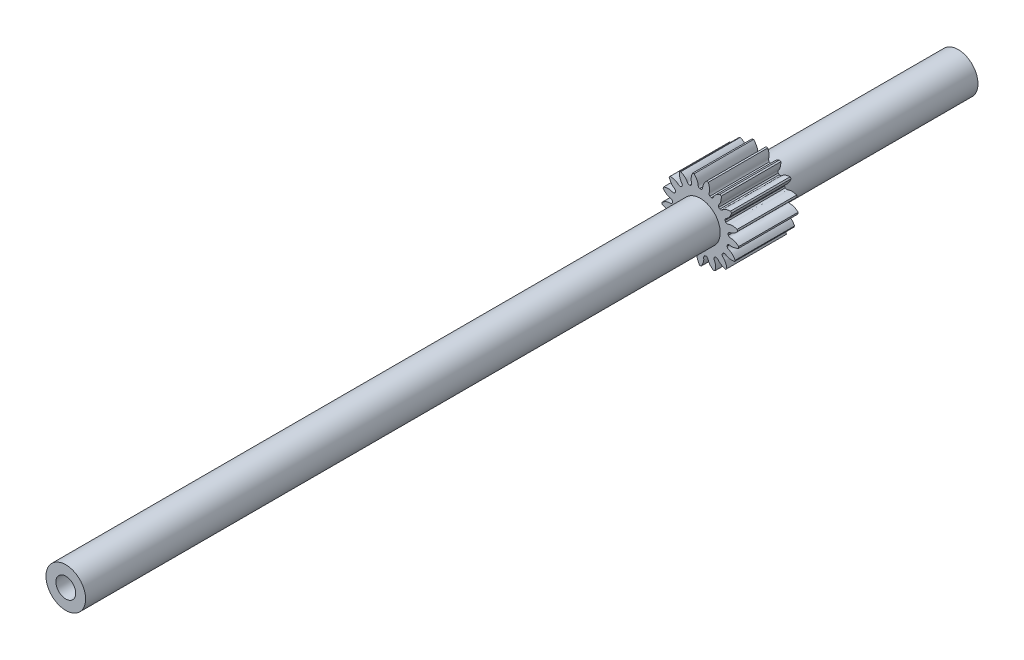
SolidWorks part; units mm, degrees
ref_plane "前视基准面" through (0, 0, 0) normal (0, 0, 1) x (1, 0, 0)
ref_plane "上视基准面" through (0, 0, 0) normal (0, 1, 0) x (1, 0, 0)
ref_plane "右视基准面" through (0, 0, 0) normal (1, 0, 0) x (0, 0, -1)
sketch "草图1" plane through (0, 0, 0) normal (0, 0, 1) x (1, 0, 0)
  circle A0 centre (0, 0) radius 19.4
extrude "凸台-拉伸1" add sketch "草图1" along normal blind 30
ref_axis "基准轴1" through (0, 0, -1.5) along (0, 0, 1)
sketch "草图2" plane through (0, 0, 0) normal (0, 0, 1) x (1, 0, 0)
  line L0 (0, 0) -> (0, 19.4) construction
  circle A0 centre (0, 0) radius 19.4 construction
  arc A1 (0.3734, 14.0951) -> (-0.3734, 14.0951) centre (0, 0) ccw
  arc A2 (7.0885, 21.9309) -> (-7.0885, 21.9309) centre (0, 0) ccw
  spline S0 degree 3 poles (0.3734, 14.0951) (1.3131, 14.5845) (1.1044, 15.3893) (1.2766, 16.1296) (1.29, 16.1823) (1.306, 16.2408) (1.3251, 16.3052) (1.3474, 16.3752) (1.3731, 16.4508) (1.4025, 16.5319) (1.4359, 16.6184) (1.4733, 16.7101) (1.5152, 16.8068) (1.5616, 16.9086) (1.6128, 17.0151) (1.669, 17.1264) (1.7304, 17.2421) (1.7972, 17.3621) (1.8696, 17.4863) (1.9478, 17.6145) (2.032, 17.7465) (2.1224, 17.8821) (2.2191, 18.0211) (2.3223, 18.1634) (2.4322, 18.3086) (2.5489, 18.4566) (2.6727, 18.6072) (2.8035, 18.7601) (2.9417, 18.9152) (3.0873, 19.0722) (3.2404, 19.2308) (3.4012, 19.3908) (3.5698, 19.552) (3.7462, 19.7141) (3.9307, 19.8769) (4.1233, 20.0401) (4.324, 20.2035) (4.533, 20.3667) (4.7503, 20.5295) (4.9761, 20.6917) (5.2103, 20.853) (5.453, 21.0131) (5.7043, 21.1717) (5.9641, 21.3286) (6.2326, 21.4834) (6.6059, 21.6888) (6.8932, 21.8358) (7.0885, 21.9309) knots 0 0 0 0 0.204302 0.208797 0.213892 0.219586 0.22588 0.232773 0.240266 0.248357 0.257049 0.266339 0.276229 0.286719 0.297808 0.309496 0.321783 0.33467 0.348157 0.362243 0.376928 0.392212 0.408096 0.42458 0.441663 0.459345 0.477626 0.496507 0.515988 0.536068 0.556747 0.578025 0.599903 0.622381 0.645457 0.669133 0.693409 0.718284 0.743758 0.769832 0.796505 0.823778 0.851649 0.880121 0.909192 0.938862 1 1 1 1
  spline S1 degree 3 poles (-0.3734, 14.0951) (-1.3131, 14.5845) (-1.1044, 15.3893) (-1.2766, 16.1296) (-1.29, 16.1823) (-1.306, 16.2408) (-1.3251, 16.3052) (-1.3474, 16.3752) (-1.3731, 16.4508) (-1.4025, 16.5319) (-1.4359, 16.6184) (-1.4733, 16.7101) (-1.5152, 16.8068) (-1.5616, 16.9086) (-1.6128, 17.0151) (-1.669, 17.1264) (-1.7304, 17.2421) (-1.7972, 17.3621) (-1.8696, 17.4863) (-1.9478, 17.6145) (-2.032, 17.7465) (-2.1224, 17.8821) (-2.2191, 18.0211) (-2.3223, 18.1634) (-2.4322, 18.3086) (-2.5489, 18.4566) (-2.6727, 18.6072) (-2.8035, 18.7601) (-2.9417, 18.9152) (-3.0873, 19.0722) (-3.2404, 19.2308) (-3.4012, 19.3908) (-3.5698, 19.552) (-3.7462, 19.7141) (-3.9307, 19.8769) (-4.1233, 20.0401) (-4.324, 20.2035) (-4.533, 20.3667) (-4.7503, 20.5295) (-4.9761, 20.6917) (-5.2103, 20.853) (-5.453, 21.0131) (-5.7043, 21.1717) (-5.9641, 21.3286) (-6.2326, 21.4834) (-6.6059, 21.6888) (-6.8932, 21.8358) (-7.0885, 21.9309) knots 0 0 0 0 0.204302 0.208797 0.213892 0.219586 0.22588 0.232773 0.240266 0.248357 0.257049 0.266339 0.276229 0.286719 0.297808 0.309496 0.321783 0.33467 0.348157 0.362243 0.376928 0.392212 0.408096 0.42458 0.441663 0.459345 0.477626 0.496507 0.515988 0.536068 0.556747 0.578025 0.599903 0.622381 0.645457 0.669133 0.693409 0.718284 0.743758 0.769832 0.796505 0.823778 0.851649 0.880121 0.909192 0.938862 1 1 1 1
extrude "切除-拉伸1" cut sketch "草图2" along normal through all
pattern_circular "阵列(圆周)1" count 17 every 21.176 about axis through (0, 0, -1.5) along (0, 0, 1) of "切除-拉伸1"
sketch "草图3" plane through (0, 0, 0) normal (0, 0, 1) x (1, 0, 0)
  circle A0 centre (0, 0) radius 17 construction
  dimension "Dn" = 34
sketch "草图4" plane through (0, 0, 0) normal (0, 0, -1) x (-1, 0, 0)
  circle A0 centre (0, 0) radius 10
  dimension "D1" = 20
extrude "凸台-拉伸2" add sketch "草图4" along normal blind 100
sketch "草图5" plane through (0, 0, 30) normal (0, 0, 1) x (1, 0, 0)
  circle A0 centre (0, 0) radius 10
  dimension "D1" = 20
extrude "凸台-拉伸3" add sketch "草图5" along normal blind 320
sketch "草图6" plane through (0, 0, -100) normal (0, 0, -1) x (-1, 0, 0)
  circle A0 centre (0, 0) radius 5
  dimension "D1" = 10
extrude "切除-拉伸2" cut sketch "草图6" against normal blind 10
sketch "草图7" plane through (0, 0, 350) normal (0, 0, 1) x (1, 0, 0)
  circle A0 centre (0, 0) radius 5
  dimension "D1" = 10
extrude "切除-拉伸3" cut sketch "草图7" against normal blind 10
